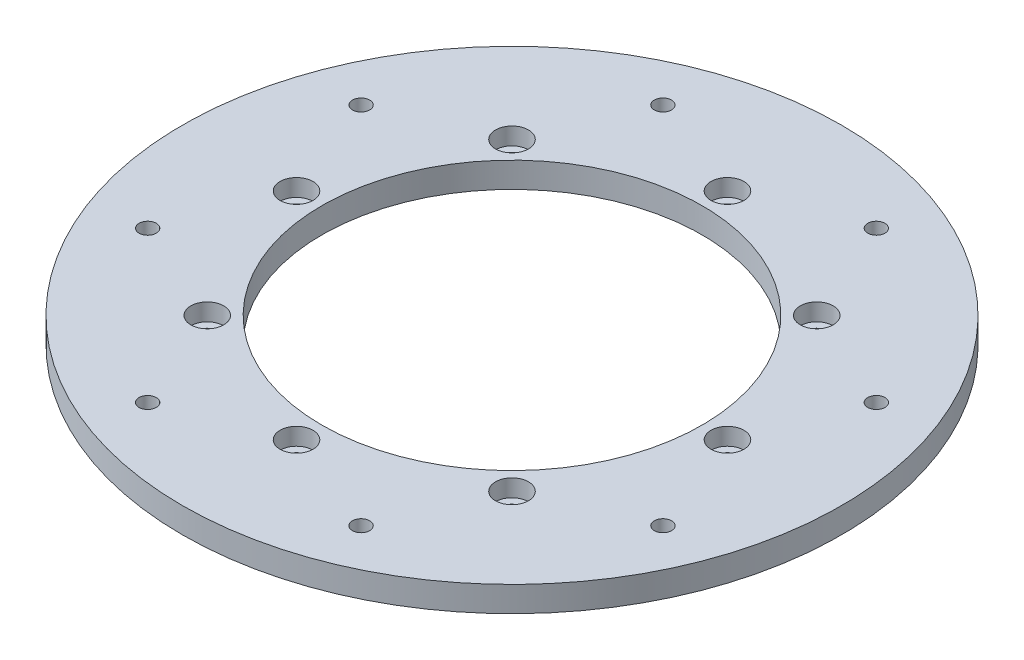
SolidWorks part; units mm, degrees
material "6061-T6 (SS)"
ref_plane "Front Plane" through (0, 0, 0) normal (0, 0, 1) x (1, 0, 0)
ref_plane "Top Plane" through (0, 0, 0) normal (0, 1, 0) x (1, 0, 0)
ref_plane "Right Plane" through (0, 0, 0) normal (1, 0, 0) x (0, 0, -1)
sketch "Sketch1" plane through (0, 0, 0) normal (0, 1, 0) x (1, 0, 0)
  circle A0 centre (0, 0) radius 37.5
  circle A1 centre (0, 0) radius 65
  dimension "D1" = 75
  dimension "D2" = 130
extrude "Boss-Extrude1" add sketch "Sketch1" along normal blind 5
sketch "Sketch4" plane through (0, 5, 0) normal (0, 1, 0) x (1, 0, 0)
  circle A0 centre (0, 0) radius 42.5 construction
  point P4 (0, 42.5)
  point P13 (30.052, 30.052)
  point P14 (42.5, 0)
  point P15 (30.052, -30.052)
  point P16 (0, -42.5)
  point P17 (-30.052, -30.052)
  point P18 (-42.5, 0)
  point P19 (-30.052, 30.052)
  dimension "D1" = 85
  dimension "D2" = 8
hole_wizard "CBORE for M3 Hex Socket Head Cap Screw1" positions "Sketch4" profile "Sketch3" counterbore size "M3" standard "DIN" end condition through all
sketch "Sketch3" plane through (-30.052, 5, -30.052) normal (1, 0, 0) x (0, 0, 1)
  line L0 (0, 0) -> (0, 5)
  line L1 (0, 5) -> (1.7, 5)
  line L3 (1.7, 5) -> (1.7, 3.4)
  line L4 (1.7, 3.4) -> (3.25, 3.4)
  line L5 (3.25, 3.4) -> (3.25, 0)
  line L7 (3.25, 0) -> (0, 0)
  line L11 (0, -6.35) -> (0, 107.95) construction
  dimension "Thru Hole Dia." = 3.4
  dimension "Thru Hole Depth" = 5
  dimension "C'Bore Dia." = 6.5
  dimension "C'Bore Depth" = 3.4
sketch "Sketch7" plane through (0, 0, 0) normal (0, -1, 0) x (-1, 0, 0)
  line L0 (0, 0) -> (-61.0389, 25.2831) construction
  circle A0 centre (0, 0) radius 55
  point P9 (-50.8134, 21.0476)
  point P17 (-21.0476, 50.8134)
  point P18 (21.0476, 50.8134)
  point P19 (50.8134, 21.0476)
  point P20 (50.8134, -21.0476)
  point P21 (21.0476, -50.8134)
  point P22 (-21.0476, -50.8134)
  point P23 (-50.8134, -21.0476)
  dimension "D1" = 22.5
  dimension "D2" = 110
  dimension "D3" = 8
hole_wizard "M3 Clearance Hole1" positions "Sketch7" profile "Sketch6" hole size "M3" standard "DIN" end condition through all
sketch "Sketch6" plane through (50.8134, 0, 21.0476) normal (1, 0, 0) x (0, 0, -1)
  line L0 (0, 0) -> (0, 5)
  line L1 (0, 5) -> (1.7, 5)
  line L2 (1.7, 5) -> (1.7, 0)
  line L5 (1.7, 0) -> (0, 0)
  line L11 (0, -6.35) -> (0, 107.95) construction
  dimension "Thru Hole Dia." = 3.4
  dimension "Thru Hole Depth" = 5
